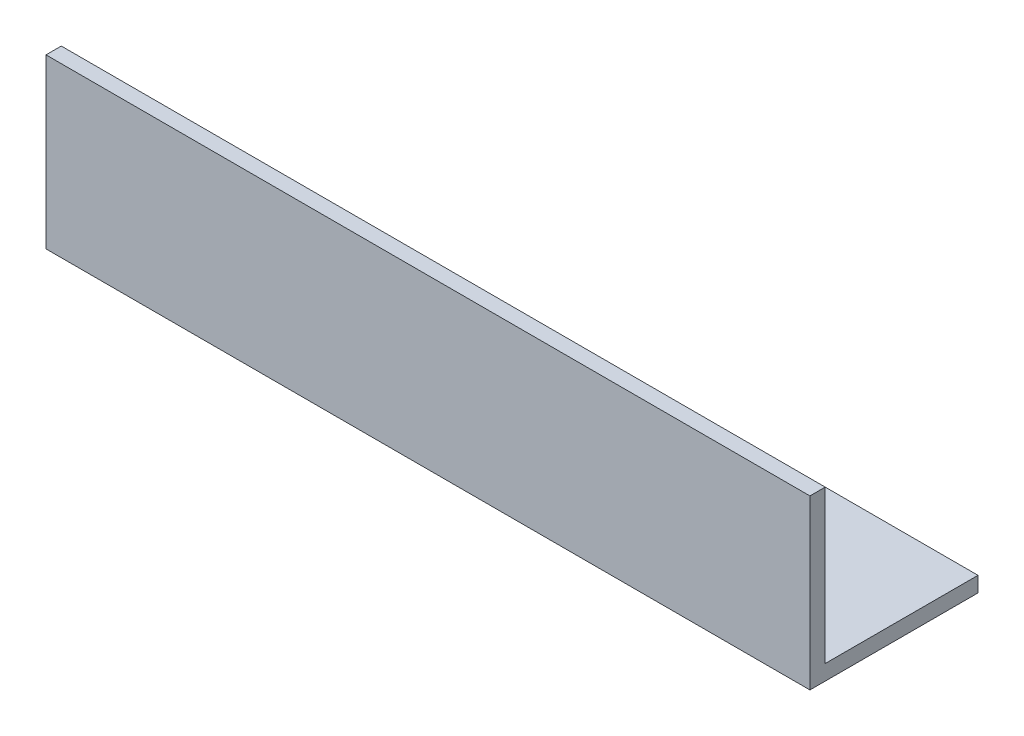
SolidWorks part; units mm, degrees
ref_plane "Спереди" through (0, 0, 0) normal (0, 0, 1) x (1, 0, 0)
ref_plane "Сверху" through (0, 0, 0) normal (0, 1, 0) x (1, 0, 0)
ref_plane "Справа" through (0, 0, 0) normal (1, 0, 0) x (0, 0, -1)
sketch "Эскиз1" plane through (0, 0, 0) normal (1, 0, 0) x (0, 0, -1)
  line L0 (0, 0) -> (0, 30)
  line L1 (0, 0) -> (30, 0)
extrude "Вытянуть-Тонкостенный1" add sketch "Эскиз1" along normal blind 150 thin thin type one direction wall 3
sketch "Эскиз2" plane through (0, -3, 0) normal (0, -1, 0) x (1, 0, 0)
  line L0 (75, -34.5488) -> (75, 3.8648) construction
  circle A0 centre (130, -12) radius 5
  circle A1 centre (100, -12) radius 5
  circle A2 centre (50, -12) radius 5
  circle A3 centre (20, -12) radius 5
  dimension "D1" = 2
extrude "Вырез-Вытянуть1" cut sketch "Эскиз2" against normal through all
